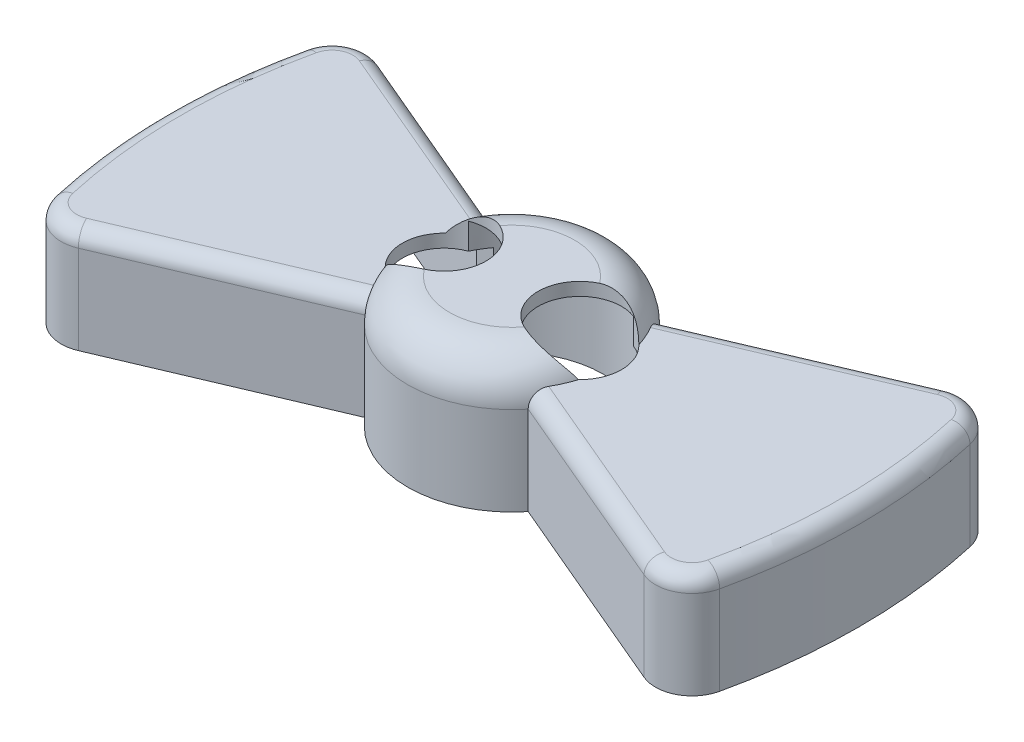
SolidWorks part; units mm, degrees
ref_plane "Front Plane" through (0, 0, 0) normal (0, 0, 1) x (1, 0, 0)
ref_plane "Top Plane" through (0, 0, 0) normal (0, 1, 0) x (1, 0, 0)
ref_plane "Right Plane" through (0, 0, 0) normal (1, 0, 0) x (0, 0, -1)
sketch "Sketch2" plane through (0, 0, 0) normal (0, 1, 0) x (1, 0, 0)
  line L0 (15.6059, 12.5082) -> (61.6311, 32.0448)
  line L1 (158.0391, 0) -> (-150.4386, 0) construction
  line L2 (-55, 0) -> (55, 0) construction
  line L3 (15.6059, -12.5082) -> (61.6311, -32.0448)
  line L4 (0, -55) -> (0, 55) construction
  line L5 (-15.6059, -12.5082) -> (-61.6311, -32.0448)
  line L6 (-15.6059, 12.5082) -> (-61.6311, 32.0448)
  line L8 (-22.75, 10.5) -> (22.75, 10.5)
  line L9 (-22.75, 10.5) -> (-22.75, -10.5)
  line L10 (-22.75, -10.5) -> (22.75, -10.5)
  line L11 (22.75, 10.5) -> (22.75, -10.5)
  line L12 (-22.75, 10.5) -> (22.75, -10.5) construction
  line L13 (-22.75, -10.5) -> (22.75, 10.5) construction
  circle A0 centre (0, 0) radius 20
  arc A1 (61.6311, -32.0448) -> (61.6311, 32.0448) centre (-42.9729, 0) ccw
  arc A2 (-61.6311, -32.0448) -> (-61.6311, 32.0448) centre (42.9729, 0) cw
  circle A3 centre (-13, 0) radius 8
  circle A4 centre (13, 0) radius 8
  point P21 (0, 0)
  point P22 (15.6059, 12.5082)
  dimension "D1" = 40
  dimension "D4" = 16
  dimension "D2" = 23
  dimension "D3" = 50
  dimension "D5" = 13
  dimension "D6" = 45.5
  dimension "D7" = 21
extrude "Boss-Extrude3" add sketch "Sketch2" along normal blind 20 contours A2 L5 A0 L10 L9 L8 L6 | L3 A1 L0 A0 L8 L11 L10 | A3 A0 L8 L9 L10 | A0 A4 L10 L11 L8 region at (45.7571, 0, 0) region at (-45.7571, 0, 0) region at (19.886, 0, -10.2823) region at (-18.6472, 0, -7.8125)
extrude "Boss-Extrude4" add sketch "Sketch2<8>" along normal blind 25 contours L8 A0 | A0 L10 | A0 A4 L8 A3 L10 | A4 | A3 region at (0, 0, -14.3898) region at (0, 0, 0) region at (0, 0, 14.3898)
sketch "Sketch2<8>" plane through (0, 0, 0) normal (0, 1, 0) x (1, 0, 0) same geometry as "Sketch2"
shell "Shell2" thickness 2.5 removed face at (0, 0, 0)
extrude "Cut-Extrude3" cut sketch "Sketch2<10>" along normal blind 17.5 contours L10 L11 L8 L9
sketch "Sketch2<10>" plane through (0, 0, 0) normal (0, 1, 0) x (1, 0, 0) same geometry as "Sketch2"
extrude "Cut-Extrude4" cut sketch "Sketch2<11>" along normal blind 25 contours A3 | A4
sketch "Sketch2<11>" plane through (0, 0, 0) normal (0, 1, 0) x (1, 0, 0) same geometry as "Sketch2"
fillet "Fillet5" radius 8 2 edges at (0, 25, 20) (0, 25, -20)
fillet "Fillet6" radius 7 8 edges at (61.6311, 10, -32.0448) (61.6311, 10, 32.0448) (-61.6311, 10, -32.0448) (-61.6311, 10, 32.0448) (60.0202, 8.75, -28.6451) (60.0202, 8.75, 28.6451) (-60.0202, 8.75, 28.6451) (-60.0202, 8.75, -28.6451)
fillet "Fillet7" radius 3 10 edges at (34.6252, 20, -20.5815) (60.1349, 20, -28.6761) (66.4294, 20, 0) (60.1349, 20, 28.6761) (-34.6252, 20, -20.5815) (-60.1349, 20, -28.6761) (-66.4294, 20, 0) (-60.1349, 20, 28.6761) (34.6252, 20, 20.5815) (-34.6252, 20, 20.5815)
